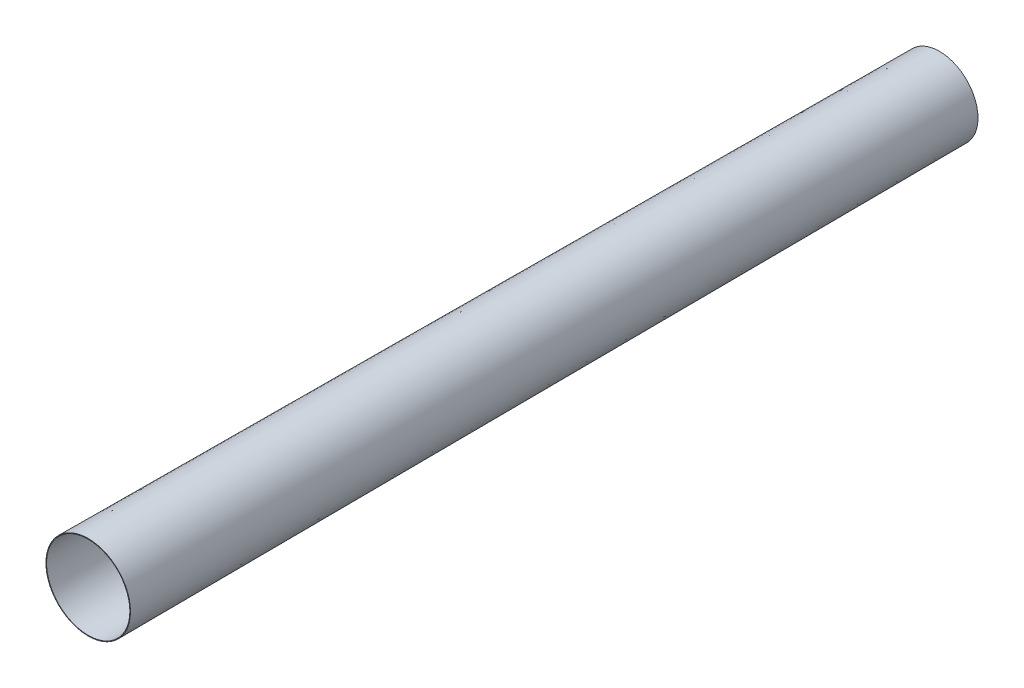
SolidWorks part; units mm, degrees
ref_plane "Front Plane" through (0, 0, 0) normal (0, 0, 1) x (1, 0, 0)
ref_plane "Top Plane" through (0, 0, 0) normal (0, 1, 0) x (1, 0, 0)
ref_plane "Right Plane" through (0, 0, 0) normal (1, 0, 0) x (0, 0, -1)
sketch "Sketch1" plane through (0, 0, 0) normal (0, 0, 1) x (1, 0, 0)
  circle A0 centre (0, 0) radius 31.2033
  circle A1 centre (0, 0) radius 31.7033
  dimension "D2" = 63.4065
  dimension "D1" = 0.5
ref_plane "Plane1" through (0, 0, 700.9946) normal (0, 0, 1) x (1, 0, 0)
sketch "Sketch2" plane through (0, 0, 700.9946) normal (0, 0, 1) x (1, 0, 0)
  circle A0 centre (0, 0) radius 34.8114
  circle A1 centre (0, 0) radius 34.3114
  dimension "D2" = 69.6229
  dimension "D1" = 0.5
loft "Loft1" add section "Sketch1" section "Sketch2" start constraint default connector at (-28.6775, -13.5166, 0) connector at (-31.5355, -14.7428, 700.9946)
shell "Shell1" thickness 0.5 removed face at (31.7033, 0, 0) removed face at (34.8114, 0, 700.9946)
